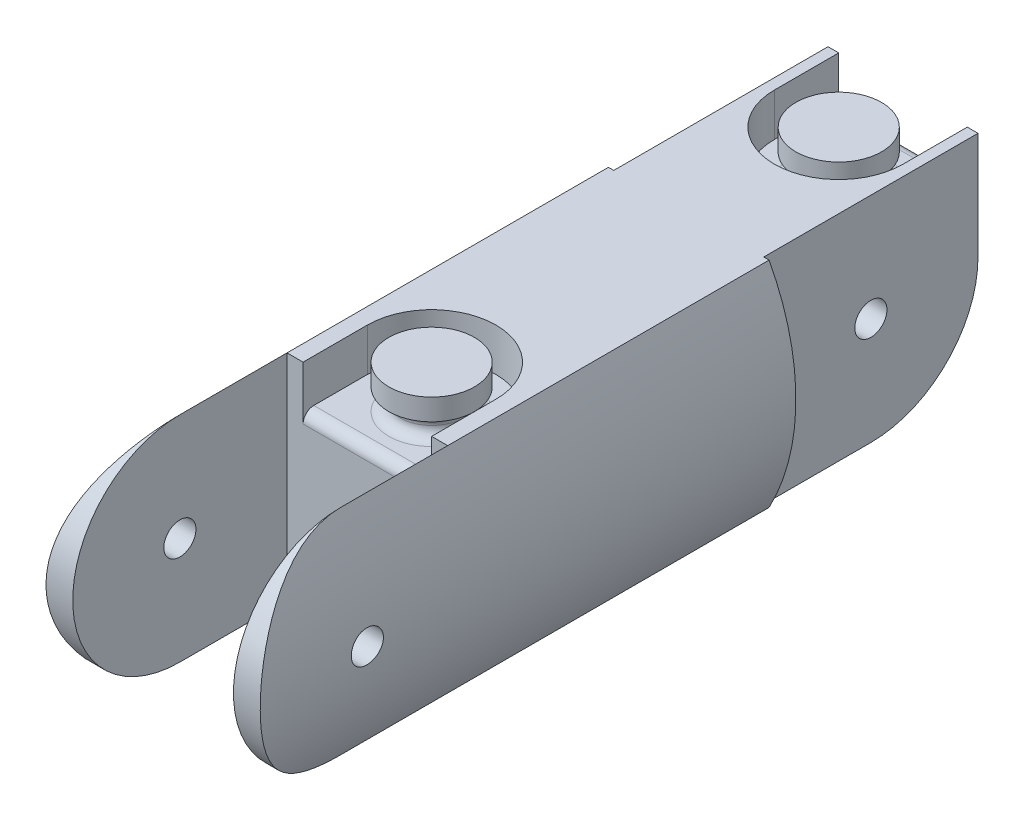
SolidWorks part; units mm, degrees
ref_plane "Alzado" through (0, 0, 0) normal (0, 0, 1) x (1, 0, 0)
ref_plane "Planta" through (0, 0, 0) normal (0, 1, 0) x (1, 0, 0)
ref_plane "Vista lateral" through (0, 0, 0) normal (1, 0, 0) x (0, 0, -1)
sketch "Croquis2" plane through (0, 0, 0) normal (0, 0, 1) x (1, 0, 0)
  line L5 (-7.5, -10) -> (7.5, -10)
  line L7 (-7.5, 10) -> (7.5, 10)
  line L9 (-7.5, -10) -> (7.5, 10) construction
  line L10 (-7.5, 10) -> (7.5, -10) construction
  arc A2 (-7.5, 10) -> (-7.5, -10) centre (11.25, 0) ccw
  arc A3 (7.5, -10) -> (7.5, 10) centre (-11.25, 0) ccw
  point P0 (0, 0)
  dimension "D1" = 15
  dimension "D2" = 20
extrude "Saliente-Extruir2" add sketch "Croquis2" along normal blind 50
sketch "Croquis4" plane through (0, 0, 0) normal (0, 0, -1) x (-1, 0, 0)
  line L1 (7.5, -10) -> (-7.5, -10) construction
  circle A0 centre (0, -7) radius 1.5
  dimension "D2" = 3
  dimension "D1" = 3
extrude "Cortar-Extruir1" cut sketch "Croquis4" against normal blind 50
sketch "Croquis3" plane through (0, 0, 0) normal (0, 0, -1) x (-1, 0, 0)
  line L8 (7.5, -10) -> (-7.5, -10) construction
  line L10 (7, 10) -> (7, -10)
  line L11 (7, -10) -> (3, -10)
  line L12 (-7, 10) -> (-7, -10)
  line L13 (7, 10) -> (-7, -10) construction
  line L14 (7, -10) -> (-7, 10) construction
  line L16 (3, -3) -> (3, -10)
  line L17 (-3, -10) -> (-7, -10)
  line L19 (-3, -3) -> (3, -3)
  line L20 (-3, -3) -> (-3, -10)
  line L21 (-7, 10) -> (7, 10)
  point P0 (0, 0)
  dimension "D1" = 14
  dimension "D2" = 4
  dimension "D3" = 4
  dimension "D4" = 7
extrude "Saliente-Extruir3" add sketch "Croquis3" along normal blind 20
sketch "Croquis8" plane through (-7, 0, 0) normal (-1, 0, 0) x (0, 0, 1)
  line L0 (-20, -10) -> (-20, 10) construction
  line L1 (-20, -10) -> (0, -10) construction
  circle A0 centre (-10, 0) radius 1.5
  point P4 (-20, 0)
  dimension "D1" = 3
  dimension "D2" = 10
  dimension "D3" = 10
extrude "Cortar-Extruir4" cut sketch "Croquis8" against normal blind 14
fillet "Redondeo1" radius 10 2 edges at (-5, -10, -20) (5, -10, -20)
sketch "Croquis6" plane through (0, 0, 50) normal (0, 0, 1) x (1, 0, 0)
  line L1 (-7.5, 10) -> (7.5, 10)
  line L2 (-7.5, 10) -> (-7.5, -10)
  line L3 (-7.5, -10) -> (7.5, -10)
  line L4 (7.5, 10) -> (7.5, -10)
extrude "Cortar-Extruir2" cut sketch "Croquis6" against normal blind 20
sketch "Croquis7" plane through (0, 0, 0) normal (1, 0, 0) x (0, 0, -1)
  line L0 (-50, 10) -> (-50, -10) construction
  line L2 (-40, -10) -> (-55, -10)
  line L4 (-40, 10) -> (-55, 10)
  line L5 (-55, -10) -> (-55, 10)
  arc A0 (-40, 10) -> (-40, -10) centre (-40, 0) ccw
  circle A1 centre (-40, 0) radius 1.5
  dimension "D3" = 10
  dimension "D4" = 3
  dimension "D1" = 10
  dimension "D2" = 15
extrude "Cortar-Extruir3" cut sketch "Croquis7" against normal through all both and the other way through all
sketch "Sketch1" plane through (0, 10, 0) normal (0, 1, 0) x (1, 0, 0)
  line L0 (7.5, -30) -> (-7.5, -30) construction
  line L1 (-7, 20) -> (7, 20) construction
  line L4 (-6, 14) -> (-6, 20)
  line L5 (-6, 20) -> (6, 20)
  line L6 (6, 14) -> (6, 20)
  line L8 (-6, -24) -> (-6, -30)
  line L9 (-6, -30) -> (6, -30)
  line L10 (6, -24) -> (6, -30)
  arc A0 (6, -24) -> (-6, -24) centre (0, -24) ccw
  arc A1 (-6, 14) -> (6, 14) centre (0, 14) ccw
  dimension "D1" = 12
  dimension "D2" = 12
  dimension "D3" = 6
  dimension "D4" = 6
extrude "Cut-Extrude1" cut sketch "Sketch1" against normal blind 4
sketch "Sketch2" plane through (0, 6, 0) normal (0, 1, 0) x (1, 0, 0)
  circle A1 centre (0, 14) radius 3
  circle A2 centre (0, -24) radius 3
  dimension "D1" = 6
  dimension "D2" = 6
extrude "Boss-Extrude1" add sketch "Sketch2" along normal blind 2
sketch "Sketch3" plane through (0, 8, 0) normal (0, 1, 0) x (1, 0, 0)
  circle A0 centre (0, -24) radius 4
  circle A1 centre (0, 14) radius 4
  dimension "D1" = 8
  dimension "D2" = 8
extrude "Boss-Extrude2" add sketch "Sketch3" along normal blind 2
fillet "Fillet1" radius 1 4 edges at (0, 8, -11) (0, 6, -11) (0, 8, 27) (0, 6, 27)
fillet "Fillet2" radius 1 2 edges at (0, 6, 30) (0, 6, -20)
fillet "Fillet3" radius 1 2 edges at (1.5, -7, 30) (-1.5, -7, 0)
